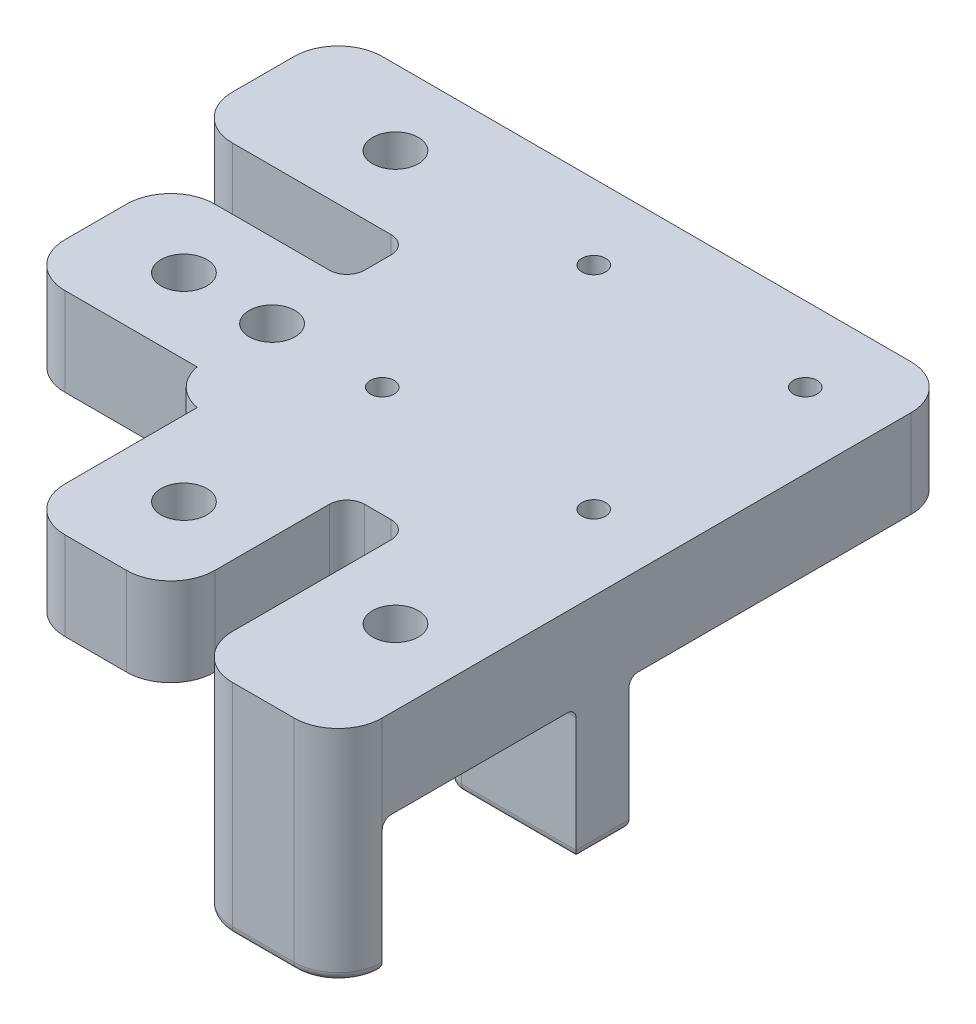
SolidWorks part; units mm, degrees
ref_plane "Front Plane" through (0, 0, 0) normal (0, 0, 1) x (1, 0, 0)
ref_plane "Top Plane" through (0, 0, 0) normal (0, 1, 0) x (1, 0, 0)
ref_plane "Right Plane" through (0, 0, 0) normal (1, 0, 0) x (0, 0, -1)
sketch "Sketch1" plane through (0, 0, 0) normal (0, 1, 0) x (1, 0, 0)
  line L1 (0, 0) -> (65, 0)
  line L2 (0, 0) -> (0, 65)
  line L3 (0, 65) -> (65, 65)
  line L4 (65, 0) -> (65, 65)
  line L5 (65, 65) -> (25, 65) construction
  line L6 (65, 65) -> (65, 25) construction
  line L7 (65, 25) -> (25, 25) construction
  line L8 (25, 65) -> (25, 25) construction
  dimension "D2" = 40
  dimension "55" = 65
extrude "Boss-Extrude2" add sketch "Sketch1" along normal blind 10
sketch "Sketch6" plane through (0, 10, 0) normal (0, 1, 0) x (1, 0, 0)
  line L0 (0, 0) -> (0, 65) construction
  line L9 (65, 65) -> (20, 65) construction
  line L10 (65, 65) -> (65, 20) construction
  line L11 (65, 20) -> (20, 20) construction
  line L12 (20, 65) -> (20, 20) construction
  line L13 (0, 0) -> (65, 0) construction
  line L14 (20, 20) -> (65, 65) construction
  line L16 (26.5, 65) -> (26.5, 26.5) construction
  line L17 (26.5, 26.5) -> (65, 26.5) construction
  line L19 (0, 65) -> (65, 65) construction
  line L20 (65, 0) -> (65, 65) construction
  line L21 (20, 50) -> (26.5, 50) construction
  line L22 (26.5, 50) -> (26.5, 45) construction
  line L23 (26.5, 45) -> (45, 26.5) construction
  line L24 (45, 26.5) -> (50, 26.5) construction
  line L25 (50, 26.5) -> (50, 20) construction
  line L27 (56.5, 56.5) -> (32.5, 56.5) construction
  line L28 (56.5, 56.5) -> (56.5, 32.5) construction
  line L29 (56.5, 32.5) -> (32.5, 32.5) construction
  line L30 (32.5, 56.5) -> (32.5, 32.5) construction
  circle A0 centre (56.5, 56.5) radius 1.35
  circle A1 centre (32.5, 56.5) radius 1.35
  circle A2 centre (32.5, 32.5) radius 1.35
  circle A3 centre (56.5, 32.5) radius 1.35
  dimension "D7" = 2.7
  dimension "D2" = 20
  dimension "D3" = 6.5
  dimension "20" = 20
  dimension "D4" = 5
  dimension "D5" = 30
  dimension "D6" = 24
  dimension "D8" = 6
extrude "Cut-Extrude3" cut sketch "Sketch6" against normal through all
sketch "Sketch7" plane through (0, 10, 0) normal (0, 1, 0) x (1, 0, 0)
  line L0 (0, 41) -> (20, 24) construction
  line L1 (0, 65) -> (20, 65) construction
  line L2 (0, 65) -> (0, 0) construction
  line L3 (0, 0) -> (20, 0) construction
  line L4 (20, 65) -> (20, 0) construction
  line L5 (65, 0) -> (65, 65) construction
  line L6 (0, 0) -> (65, 0) construction
  line L7 (0, 0) -> (0, 20) construction
  line L8 (0, 20) -> (65, 20) construction
  line L9 (65, 0) -> (65, 20) construction
  line L10 (10, 65) -> (10, 0) construction
  line L11 (65, 10) -> (0, 10) construction
  line L12 (56.5, 56.5) -> (10, 56.5) construction
  line L13 (56.5, 10) -> (56.5, 56.5) construction
  line L14 (10, 32.5) -> (32.5, 32.5) construction
  line L15 (32.5, 32.5) -> (32.5, 10) construction
  line L16 (48, 20) -> (65, 0) construction
  line L29 (32.5, 10) -> (44.5, 10) construction
  line L30 (44.5, 10) -> (56.5, 10) construction
  line L31 (0, 48) -> (20, 48)
  line L32 (10, 56.5) -> (10, 44.5) construction
  line L33 (10, 44.5) -> (10, 32.5) construction
  line L34 (0, 48) -> (0, 41)
  line L35 (0, 41) -> (20, 41)
  line L36 (20, 48) -> (20, 41)
  line L37 (41, 20) -> (48, 20)
  line L38 (41, 20) -> (41, 0)
  line L39 (41, 0) -> (48, 0)
  line L40 (48, 20) -> (48, 0)
  line L41 (41, 20) -> (24, 0) construction
  line L42 (0, 48) -> (20, 65) construction
  line L43 (0, 24) -> (20, 24)
  line L44 (0, 24) -> (0, 20)
  line L46 (20, 24) -> (20, 20)
  line L47 (0, 0) -> (20, 0)
  line L48 (0, 0) -> (0, 20)
  line L51 (20, 0) -> (24, 0)
  line L53 (20, 20) -> (24, 20)
  line L54 (24, 0) -> (24, 20)
  circle A0 centre (10, 32.5) radius 2.6
  circle A1 centre (10, 56.5) radius 2.6
  circle A2 centre (32.5, 10) radius 2.6
  circle A3 centre (56.5, 10) radius 2.6
  dimension "D2" = 5.2
  dimension "D1" = 20
  dimension "D3" = 17
  dimension "D4" = 17
extrude "Cut-Extrude4" cut sketch "Sketch7" against normal through all
sketch "Sketch9" plane through (0, 0, 0) normal (0, -1, 0) x (1, 0, 0)
  line L1 (20, -20) -> (65, -20) construction
  line L2 (20, -20) -> (20, -65) construction
  line L3 (20, -65) -> (65, -65) construction
  line L4 (65, -20) -> (65, -65) construction
  line L5 (65, -65) -> (26.5, -65) construction
  line L6 (65, -65) -> (65, -26.5) construction
  line L7 (65, -26.5) -> (26.5, -26.5) construction
  line L8 (26.5, -65) -> (26.5, -26.5) construction
  line L9 (20, -20) -> (50, -20) construction
  line L10 (20, -20) -> (20, -50) construction
  line L11 (20, -50) -> (50, -50) construction
  line L12 (50, -20) -> (50, -50) construction
  line L21 (50, -22) -> (65, -22)
  line L22 (50, -22) -> (50, -28)
  line L23 (50, -28) -> (65, -28)
  line L24 (65, -22) -> (65, -28)
  line L25 (22, -50) -> (28, -50)
  line L26 (22, -50) -> (22, -65)
  line L27 (22, -65) -> (28, -65)
  line L28 (28, -50) -> (28, -65)
  dimension "D1" = 6.5
  dimension "D2" = 30
  dimension "D3" = 2
  dimension "D4" = 2
  dimension "D5" = 6
extrude "Boss-Extrude5" add sketch "Sketch9" along normal blind 15
fillet "Fillet4" radius 2 8 edges at (22, -7.5, -50) (28, -7.5, -50) (50, -7.5, -28) (50, -7.5, -22) (48, 5, -20) (41, 5, -20) (20, 5, -41) (20, 5, -48)
fillet "Fillet5" radius 1 10 edges at (58.5, 0, -22) (50.5858, 0, -22.5858) (58.5, 0, -28) (50.5858, 0, -27.4142) (28, 0, -58.5) (27.4142, 0, -50.5858) (22, 0, -58.5) (22.5858, 0, -50.5858) (50, 0, -25) (25, 0, -50)
fillet "Fillet6" radius 1 12 edges at (27.4142, -15, -50.5858) (28, -15, -58.5) (25, -15, -65) (22, -15, -58.5) (22.5858, -15, -50.5858) (25, -15, -50) (50.5858, -15, -22.5858) (58.5, -15, -22) (65, -15, -25) (58.5, -15, -28) (50.5858, -15, -27.4142) (50, -15, -25)
sketch "Sketch10" plane through (0, 0, 0) normal (0, -1, 0) x (1, 0, 0)
  line L0 (0, -65) -> (21, -65) construction
  line L1 (48, 0) -> (65, 0)
  line L2 (48, 0) -> (48, 5)
  line L3 (48, 5) -> (65, 5)
  line L4 (65, 0) -> (65, 5)
  line L5 (0, -48) -> (-5, -48)
  line L6 (0, -48) -> (0, -65)
  line L7 (0, -65) -> (-5, -65)
  line L8 (-5, -48) -> (-5, -65)
  line L9 (65, 0) -> (65, -21) construction
  dimension "D1" = 5
  dimension "D2" = 5
extrude "Boss-Extrude6" add sketch "Sketch10" along normal blind 15 and the other way up to surface (10 mm away) other way up to face at (10, 10, -29.9)
fillet "Fillet7" radius 5 10 edges at (65, 5, -65) (65, -2.5, 5) (48, -2.5, 5) (41, 5, 0) (20, 5, -20) (24, 5, 0) (0, 5, -24) (0, 5, -41) (-5, -2.5, -48) (-5, -2.5, -65)
fillet "Fillet8" radius 1 10 edges at (49.4645, -15, 3.5355) (56.5, -15, 5) (63.5355, -15, 3.5355) (56.5, -15, 0) (-3.5355, -15, -63.5355) (-5, -15, -56.5) (-3.5355, -15, -49.4645) (0, -15, -56.5) (56.5, 0, 0) (0, 0, -56.5)
sketch "Sketch11" plane through (0, 10, 0) normal (0, 1, 0) x (1, 0, 0)
  line L0 (10, 32.5) -> (20, 32.5) construction
  circle A0 centre (20, 32.5) radius 2.6
  dimension "D1" = 5.2
  dimension "D2" = 10
extrude "Cut-Extrude5" cut sketch "Sketch11" against normal through all
